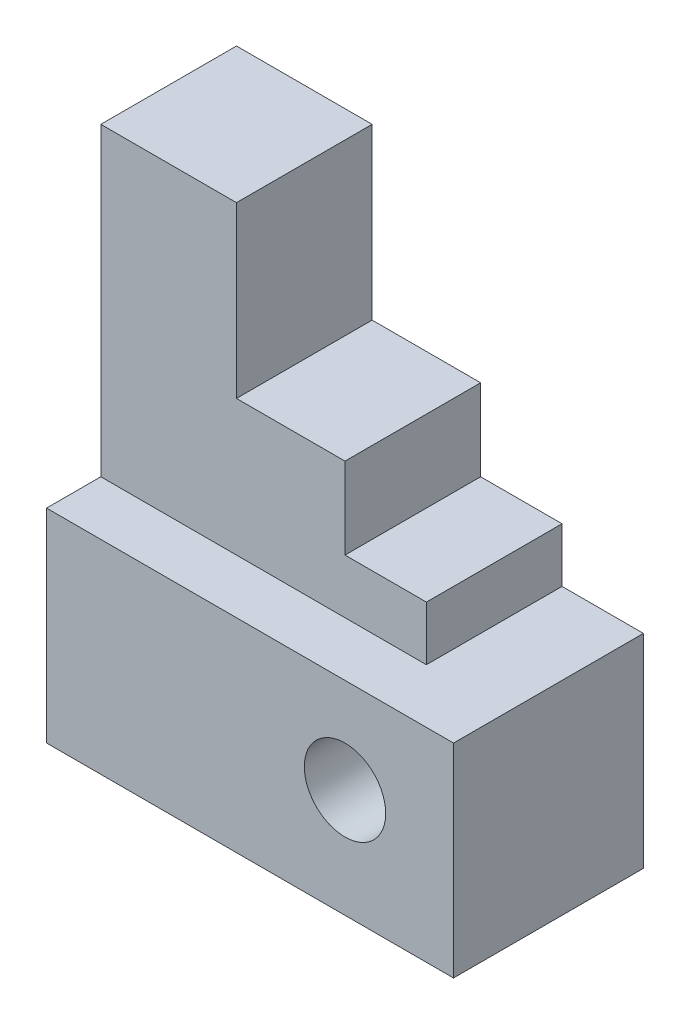
SolidWorks part; units mm, degrees
material "ABS"
ref_plane "Front Plane" through (0, 0, 0) normal (0, 0, 1) x (1, 0, 0)
ref_plane "Top Plane" through (0, 0, 0) normal (0, 1, 0) x (1, 0, 0)
ref_plane "Right Plane" through (0, 0, 0) normal (1, 0, 0) x (0, 0, -1)
sketch "Sketch2" plane through (0, 0, 0) normal (0, 0, 1) x (1, 0, 0)
  line L1 (0, 0) -> (-60, 0)
  line L2 (0, 0) -> (0, 30)
  line L3 (0, 30) -> (-60, 30)
  line L4 (-60, 0) -> (-60, 30)
  line L5 (-60, 30) -> (-12, 30)
  line L6 (-60, 30) -> (-60, 50)
  line L7 (-60, 50) -> (-24, 50)
  line L8 (-12, 30) -> (-12, 38)
  line L9 (-24, 50) -> (-24, 38)
  line L10 (-24, 38) -> (-12, 38)
  line L11 (0, 0) -> (-16, 0)
  line L12 (-60, 50) -> (-40, 50)
  line L13 (-60, 50) -> (-60, 75)
  line L14 (-60, 75) -> (-40, 75)
  line L15 (-40, 50) -> (-40, 75)
  circle A0 centre (-16, 16) radius 6
  point P15 (0, 0)
  point P17 (0, 0)
  dimension "D7" = 12
  dimension "D1" = 60
  dimension "D2" = 30
  dimension "D3" = 25
  dimension "D4" = 20
  dimension "D5" = 20
  dimension "D6" = 12
extrude "Boss-Extrude2" add sketch "Sketch2" against normal blind 28 contours L4 L1 L2 L3 A0 | L10 L9 L7 L6 L3 L8 | L7 L15 L14 L13 region at (-30.9386, 14.933, 0) region at (-39.1765, 39.2941, 0) region at (-50, 62.5, 0)
extrude "Cut-Extrude1" cut sketch "Sketch2<11>" against normal blind 8 contours L10 L9 L7 L6 L3 L8 | L7 L15 L14 L13 region at (-39.1765, 39.2941, 0) region at (-50, 62.5, 0)
sketch "Sketch2<11>" plane through (0, 0, 0) normal (0, 0, 1) x (1, 0, 0) same geometry as "Sketch2"
